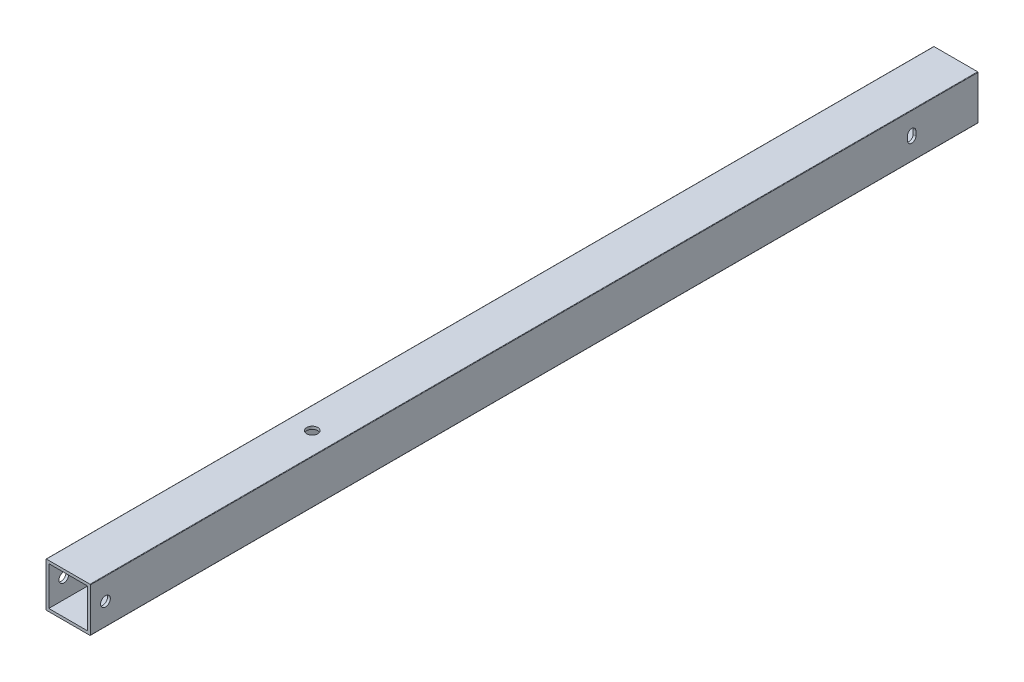
SolidWorks part; units mm, degrees
material "1060 Alloy"
ref_plane "Front Plane" through (0, 0, 0) normal (0, 0, 1) x (1, 0, 0)
ref_plane "Top Plane" through (0, 0, 0) normal (0, 1, 0) x (1, 0, 0)
ref_plane "Right Plane" through (0, 0, 0) normal (1, 0, 0) x (0, 0, -1)
ref_plane "Plane1" through (0, 0, 0) normal (0, 0, -1) x (-1, 0, 0)
sketch "Sketch1" plane through (0, 0, 0) normal (0, 0, -1) x (-1, 0, 0)
  line L4 (1.5875, -1.3335) -> (1.5875, 23.5585)
  line L5 (1.3335, 23.8125) -> (-23.5585, 23.8125)
  line L6 (-23.8125, 23.5585) -> (-23.8125, -1.3335)
  line L7 (-23.5585, -1.5875) -> (1.3335, -1.5875)
  line L9 (0, 22.225) -> (-22.225, 22.225)
  line L10 (0, 22.225) -> (0, 0)
  line L11 (0, 0) -> (-22.225, 0)
  line L12 (-22.225, 22.225) -> (-22.225, 0)
  line L13 (0, 22.225) -> (-22.225, 0) construction
  line L14 (0, 0) -> (-22.225, 22.225) construction
  arc A4 (1.3335, -1.5875) -> (1.5875, -1.3335) centre (1.3335, -1.3335) ccw
  arc A5 (1.5875, 23.5585) -> (1.3335, 23.8125) centre (1.3335, 23.5585) ccw
  arc A6 (-23.5585, 23.8125) -> (-23.8125, 23.5585) centre (-23.5585, 23.5585) ccw
  arc A7 (-23.8125, -1.3335) -> (-23.5585, -1.5875) centre (-23.5585, -1.3335) ccw
  point P24 (-11.1125, 11.1125)
  dimension "D1" = 25.4
  dimension "D2" = 25.4
  dimension "D3" = 1.5875
  dimension "D4" = 1.5875
  dimension "D5" = 1.5875
extrude "Boss-Extrude1" add sketch "Sketch1" against normal blind 508
sketch "Sketch2" plane through (-1.5875, 0, 0) normal (-1, 0, 0) x (0, 0, 1)
  line L0 (0, -1.3335) -> (0, 23.5585) construction
  line L1 (508, -1.3335) -> (0, -1.3335) construction
  line L2 (508, -1.3335) -> (508, 23.5585) construction
  circle A0 centre (12.6975, 11.3665) radius 1.5875
  circle A1 centre (495.3, 11.3665) radius 1.5875
  circle A2 centre (76.2, 11.3665) radius 6.35
  circle A3 centre (431.8, 11.3665) radius 6.35
  point P4 (0, 11.1125)
  dimension "D1" = 3.175
  dimension "D2" = 12.7
  dimension "D3" = 12.7
  dimension "D4" = 3.175
  dimension "D5" = 12.7
  dimension "D6" = 12.7
  dimension "D7" = 12.7
  dimension "D8" = 12.7
  dimension "D9" = 76.2
  dimension "D10" = 12.7
  dimension "D11" = 12.7
  dimension "D12" = 76.2
extrude "Cut-Extrude1" [suppressed] cut sketch "Sketch2" against normal through all
sketch "Sketch4" plane through (23.8125, 0, 0) normal (1, 0, 0) x (0, 0, -1)
  line L2 (-40.3145, 9.8425) -> (-40.3145, 12.3825)
  line L4 (-35.552, 9.8425) -> (-35.552, 12.3825)
  line L6 (-40.3145, 12.3825) -> (-35.552, 12.3825)
  line L7 (-40.3145, 11.1125) -> (-35.552, 11.1125)
  line L8 (0, 23.5585) -> (0, -1.3335) construction
  line L9 (0, 11.1125) -> (-49.6378, 11.1125)
  circle A0 centre (-37.9333, 9.8425) radius 2.3812
  circle A1 centre (-37.9333, 12.3825) radius 2.3812
  dimension "D1" = 4.7625
  dimension "D2" = 37.9333
  dimension "D3" = 1.27
extrude "Cut-Extrude2" cut sketch "Sketch4" against normal through all contours L6 A1 | L6 A1 A0 | L9 A0 | L9 A1 | A1 A0 | A0 L4 L7 | A1 L7 L4 | A0 L7 L2 | A1 L2 L7 | A0 region at (23.8125, 9.1445, 37.9333) region at (23.8125, 10.8001, 40.2061) region at (23.8125, 11.4249, 40.2061) region at (23.8125, 10.8001, 35.6605) region at (23.8125, 11.5673, 37.9333) region at (23.8125, 11.7352, 40.1736) region at (23.8125, 10.6577, 37.9333) region at (23.8125, 13.3931, 37.9333) region at (23.8125, 11.4249, 35.6605)
sketch "Sketch5" plane through (23.8125, 0, 0) normal (1, 0, 0) x (0, 0, -1)
  line L0 (-508, 23.5585) -> (-508, -1.3335) construction
  line L1 (-508, 23.8125) -> (0, 23.8125) construction
  circle A0 centre (-499.364, 11.1125) radius 2.794
  dimension "D1" = 8.636
  dimension "D2" = 12.7
extrude "Cut-Extrude3" cut sketch "Sketch5" against normal blind 25.4
sketch "Sketch6" plane through (0, -1.5875, 0) normal (0, -1, 0) x (1, 0, 0)
  line L0 (11.1125, 508) -> (11.1125, 368.3) construction
  line L1 (23.5585, 508) -> (-1.3335, 508) construction
  circle A0 centre (11.1125, 368.3) radius 3.175
  dimension "D2" = 6.35
  dimension "D1" = 139.7
extrude "Cut-Extrude4" cut sketch "Sketch6" against normal through all
